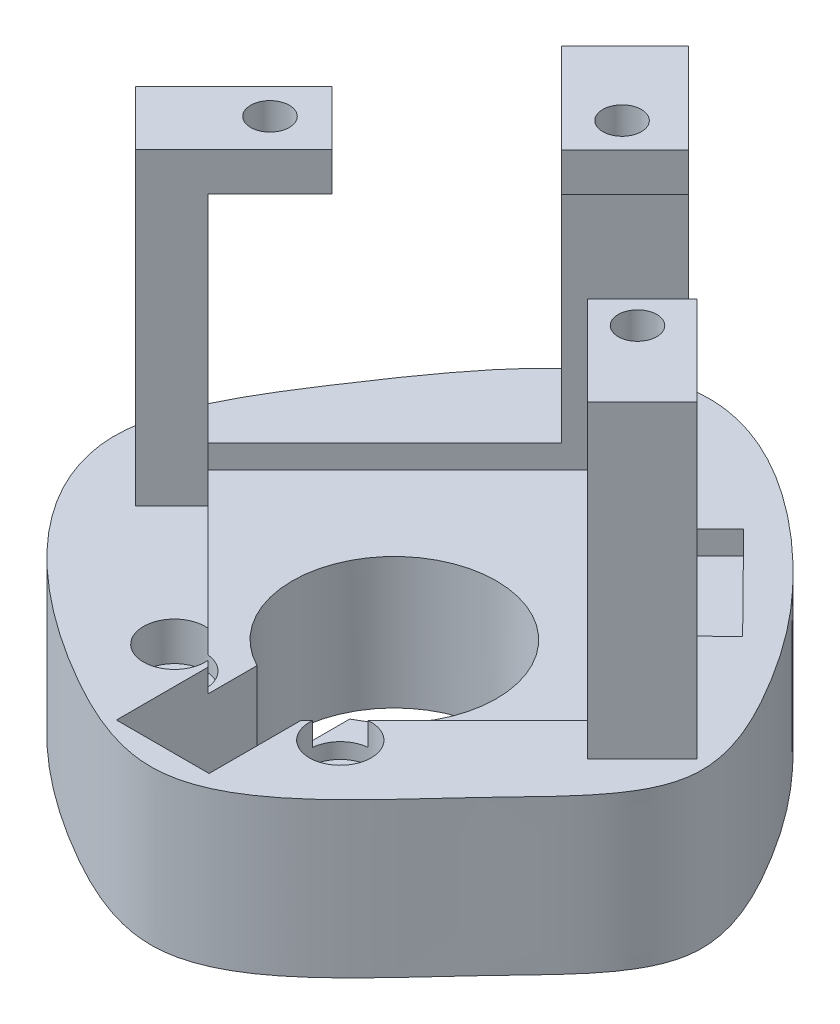
SolidWorks part; units mm, degrees
ref_plane "Front Plane" through (0, 0, 0) normal (0, 0, 1) x (1, 0, 0)
ref_plane "Top Plane" through (0, 0, 0) normal (0, 1, 0) x (1, 0, 0)
ref_plane "Right Plane" through (0, 0, 0) normal (1, 0, 0) x (0, 0, -1)
sketch "Sketch2" plane through (0, 0, 0) normal (0, 1, 0) x (1, 0, 0)
  circle A0 centre (0, 0) radius 60
extrude "Boss-Extrude1" add sketch "Sketch2" along normal blind 10 and the other way blind 10 contours A0
sketch "Sketch4" plane through (0, 10, 0) normal (0, 1, 0) x (1, 0, 0)
  circle A1 centre (0, 10) radius 13.225
sketch "Sketch6" plane through (0, 10, 0) normal (0, 1, 0) x (1, 0, 0)
  line L0 (-5.9779, 23.0428) -> (5.9779, 10.9572)
  line L1 (-5.9779, 23.0428) -> (13.2168, 42.0313)
  line L2 (5.9779, 10.9572) -> (25.1725, 29.9458)
  line L3 (13.2168, 42.0313) -> (25.1725, 29.9458)
  point P2 (15.5752, 20.4515)
  point P5 (3.6195, 32.537)
  dimension "D1" = 17
  dimension "D2" = 27
sketch "Sketch7" plane through (0, 10, 0) normal (0, 1, 0) x (1, 0, 0)
  circle A0 centre (-10.75, -7.75) radius 4
  point P2 (0, 0)
  point P3 (0, 0)
  point P4 (0, 0)
  dimension "D1" = 8
extrude "Cut-Extrude2" cut sketch "Sketch7" against normal blind 5 contours A0
mirror "Mirror1" about plane through (0, 0, 0) normal (1, 0, 0) of "Cut-Extrude2"
sketch "Sketch9" plane through (0, 10, 0) normal (0, 1, 0) x (1, 0, 0)
  line L0 (-31.1127, 17) -> (0, 48.1127)
  line L1 (-31.1127, 17) -> (0, -14.1127)
  line L2 (0, 48.1127) -> (31.1127, 17)
  line L3 (0, -14.1127) -> (31.1127, 17)
  dimension "D1" = 44
  dimension "D2" = 44
extrude "Cut-Extrude4" cut sketch "Sketch9" against normal blind 3
extrude "Cut-Extrude5" cut sketch "Sketch6" against normal blind 3
sketch "Sketch11" plane through (0, 10, 0) normal (0, 1, 0) x (1, 0, 0)
  line L0 (0, 48.1127) -> (-8.24, 39.8727)
  line L1 (0, 48.1127) -> (-4.5593, 52.672)
  line L2 (-8.24, 39.8727) -> (-12.7993, 44.432)
  line L3 (-4.5593, 52.672) -> (-12.7993, 44.432)
  line L4 (-31.1127, 17) -> (-24.0416, 9.9289)
  line L5 (-31.1127, 17) -> (-35.8263, 12.2864)
  line L6 (-24.0416, 9.9289) -> (-28.7552, 5.2154)
  line L7 (-35.8263, 12.2864) -> (-28.7552, 5.2154)
  line L8 (-31.1127, 17) -> (-10.3418, -3.7709) construction
  line L9 (31.6446, 17.5319) -> (24.5735, 10.4608)
  line L10 (31.6446, 17.5319) -> (35.9355, 13.241)
  line L11 (24.5735, 10.4608) -> (28.8645, 6.1699)
  line L12 (35.9355, 13.241) -> (28.8645, 6.1699)
  line L13 (10.3418, -3.7709) -> (31.1127, 17) construction
  line L14 (0, 48.1127) -> (-31.1127, 17) construction
  dimension "D1" = 11.6531
  dimension "D2" = 10
  dimension "D3" = 10
extrude "Boss-Extrude2" add sketch "Sketch11" along normal blind 35
sketch "Sketch12" plane through (0, 45, 0) normal (0, 1, 0) x (1, 0, 0)
  line L0 (-4.5593, 52.672) -> (-12.7993, 44.432)
  line L1 (-4.5593, 52.672) -> (7.108, 41.0047)
  line L2 (-12.7993, 44.432) -> (-1.132, 32.7647)
  line L3 (7.108, 41.0047) -> (-1.132, 32.7647)
  line L4 (-35.8263, 12.2864) -> (-28.7552, 5.2154)
  line L5 (-35.8263, 12.2864) -> (-23.0984, 25.0143)
  line L6 (-28.7552, 5.2154) -> (-16.0273, 17.9433)
  line L7 (-23.0984, 25.0143) -> (-16.0273, 17.9433)
  line L8 (35.9355, 13.241) -> (28.8645, 6.1699)
  line L9 (35.9355, 13.241) -> (24.3378, 24.8387)
  line L10 (28.8645, 6.1699) -> (17.2667, 17.7677)
  line L11 (24.3378, 24.8387) -> (17.2667, 17.7677)
extrude "Boss-Extrude3" add sketch "Sketch12" along normal blind 5
sketch "Sketch13" plane through (0, 50, 0) normal (0, 1, 0) x (1, 0, 0)
  circle A0 centre (-0.5, 40) radius 2.5
  dimension "D1" = 5
sketch "Sketch14" plane through (0, 50, 0) normal (0, 1, 0) x (1, 0, 0)
  circle A0 centre (23.5, 18) radius 2.5
sketch "Sketch15" plane through (0, 50, 0) normal (0, 1, 0) x (1, 0, 0)
  circle A0 centre (-23.777, 17.669) radius 2.5
extrude "Cut-Extrude7" cut sketch "Sketch13" against normal blind 5 contours A0
extrude "Cut-Extrude8" cut sketch "Sketch15" against normal blind 5 contours A0
extrude "Cut-Extrude9" cut sketch "Sketch14" against normal blind 5 contours A0
sketch "Sketch16" plane through (0, 10, 0) normal (0, 1, 0) x (1, 0, 0)
  spline S0 degree 3 poles (-27.5345, 35.3123) (-7.4919, 63.2621) (20.1768, 43.1639) (32.0959, 27.7397) (41.1035, 9.3847) (23.4414, -7.0123) (7.3872, -27.6695) (-20.6756, -15.2656) (-45.2159, 6.8631) (-27.5345, 35.3123) (-7.4919, 63.2621) (20.1768, 43.1639) knots -0.41993 -0.246246 -0.147029 0 0.129983 0.21607 0.283536 0.368924 0.507401 0.58007 0.753754 0.852971 1 1.129983 1.21607 1.283536 only from (-4.7945, 54.4115) to (-4.7945, 54.4115)
  circle M1 centre (0, 0) radius 60
extrude "Cut-Extrude10" cut sketch "Sketch16" against normal blind 38 contours S0 M1 | S0 region at (-58.3029, 10, 0)
extrude "Cut-Extrude12" cut sketch "Sketch4" against normal blind 42 contours A1
sketch "Sketch19" plane through (0, 10, 0) normal (0, 1, 0) x (1, 0, 0)
  line L0 (-6, 0) -> (-6, -20)
  line L1 (-6, 0) -> (6, 0)
  line L2 (-6, -20) -> (6, -20)
  line L3 (6, 0) -> (6, -20)
  point P0 (0, 0)
extrude "Cut-Extrude13" cut sketch "Sketch19" against normal blind 17
